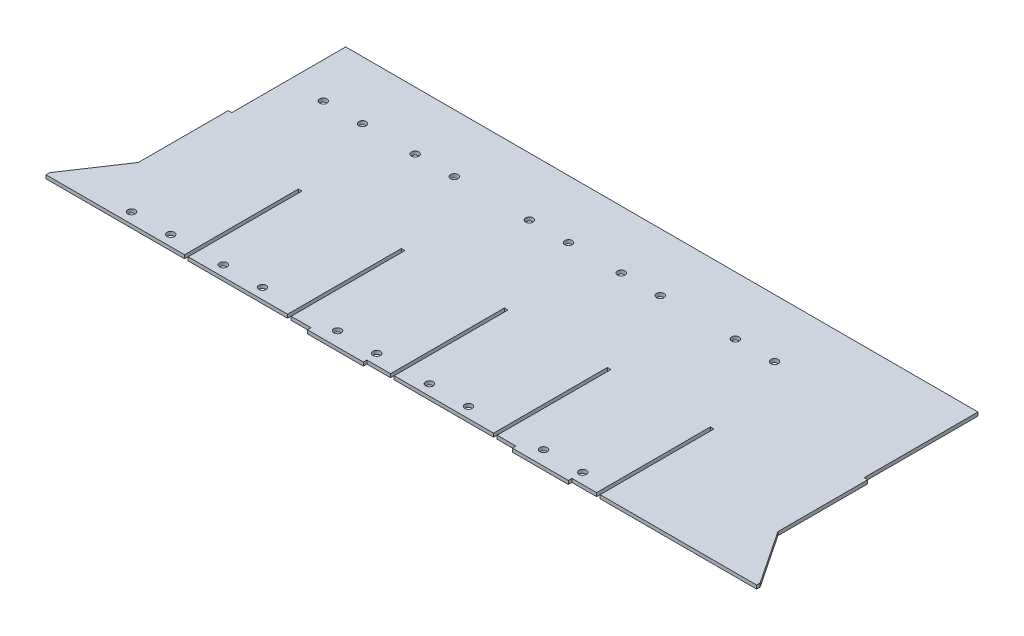
SolidWorks part; units mm, degrees
material "6061-T6 (SS)"
ref_plane "X-Y Datum" through (0, 0, 0) normal (0, 0, 1) x (1, 0, 0)
ref_plane "X-Z Datum" through (0, 0, 0) normal (0, 1, 0) x (1, 0, 0)
ref_plane "Y-Z Datum" through (0, 0, 0) normal (1, 0, 0) x (0, 0, -1)
sketch "Sketch1" plane through (0, 0, 0) normal (0, 0, 1) x (1, 0, 0)
  line L1 (-285.4305, -1.5875) -> (285.4305, -1.5875)
  line L2 (-285.4305, -1.5875) -> (-285.4305, 1.5875)
  line L3 (-285.4305, 1.5875) -> (285.4305, 1.5875)
  line L4 (285.4305, -1.5875) -> (285.4305, 1.5875)
  line L5 (-285.4305, -1.5875) -> (285.4305, 1.5875) construction
  line L6 (-285.4305, 1.5875) -> (285.4305, -1.5875) construction
  point P0 (0, 0)
  dimension "D1" = 570.861
  dimension "D2" = 3.175
extrude "Boss-Extrude1" add sketch "Sketch1" along normal blind 232.6
sketch "Sketch2" plane through (0, 1.5875, 0) normal (0, 1, 0) x (1, 0, 0)
  line L0 (-176.5505, -181.8) -> (-285.4305, -181.8) construction
  line L1 (-285.4305, -232.6) -> (-285.4305, 0) construction
  line L3 (285.4305, -232.6) -> (-285.4305, -232.6) construction
  line L4 (-178.0615, -232.6) -> (-174.8865, -232.6)
  line L6 (-178.0615, -118.3) -> (-174.8865, -118.3)
  line L8 (-178.0615, -232.6) -> (-174.8865, -232.6)
  line L9 (-178.0615, -232.6) -> (-178.0615, -118.3)
  line L10 (-178.0615, -118.3) -> (-174.8865, -118.3)
  line L11 (-174.8865, -232.6) -> (-174.8865, -118.3)
  line L17 (-178.0615, -118.3) -> (-174.8865, -118.3)
  line L38 (-285.4305, 0) -> (-282.2555, 0)
  line L39 (-285.4305, 0) -> (-285.4305, -101.6)
  line L40 (-285.4305, -101.6) -> (-282.2555, -101.6)
  line L41 (-282.2555, 0) -> (-282.2555, -101.6)
  line L42 (285.4305, 0) -> (282.2555, 0)
  line L43 (285.4305, 0) -> (285.4305, -101.6)
  line L44 (285.4305, -101.6) -> (282.2555, -101.6)
  line L45 (282.2555, 0) -> (282.2555, -101.6)
  line M3 (285.4305, 0) -> (-285.4305, 0)
  line M4 (-285.4305, 0) -> (-285.4305, -232.6)
  line M6 (285.4305, -232.6) -> (285.4305, 0)
  dimension "D2" = 50.8
  dimension "D3" = 3.175
  dimension "D6" = 3.175
  dimension "D7" = 101.6
  dimension "D4" = 114.3
  dimension "D8" = 3.175
  dimension "D9" = 101.6
sketch "Sketch6" plane through (0, 0, 232.6) normal (0, 0, 1) x (1, 0, 0)
  line L0 (285.4305, 1.5875) -> (-285.4305, 1.5875) construction
  line L1 (-285.4305, 1.5875) -> (-285.4305, -1.5875) construction
  line L14 (152.263, -1.5875) -> (152.263, 1.5875)
  line L15 (102.263, 1.5875) -> (152.263, 1.5875)
  line L16 (102.263, -1.5875) -> (152.263, 1.5875) construction
  line L17 (102.263, 1.5875) -> (152.263, -1.5875) construction
  line L18 (102.263, -1.5875) -> (152.263, -1.5875)
  line L19 (102.263, -1.5875) -> (102.263, 1.5875)
  line L20 (-30.6951, -1.5875) -> (-30.6951, 1.5875)
  line L21 (-80.6951, 1.5875) -> (-30.6951, 1.5875)
  line L22 (-80.6951, -1.5875) -> (-30.6951, 1.5875) construction
  line L23 (-80.6951, 1.5875) -> (-30.6951, -1.5875) construction
  line L24 (-80.6951, -1.5875) -> (-30.6951, -1.5875)
  line L25 (-80.6951, -1.5875) -> (-80.6951, 1.5875)
  point P4 (-55.6951, 0)
  point P5 (127.263, 0)
  dimension "D1" = 3.175
  dimension "D2" = 50
  dimension "D3" = 3.175
  dimension "D4" = 229.7354
  dimension "D5" = 182.9581
sketch "Sketch7" plane through (0, -1.5875, 0) normal (0, -1, 0) x (-1, 0, 0)
  line L1 (-285.4305, -232.6) -> (-285.4305, 0) construction
  circle A2 centre (-245.6805, -11.2916) radius 3.302
  dimension "D1" = 39.75
  dimension "D2" = 6.604
extrude "Cut-Extrude4" [suppressed] cut sketch "Sketch7" against normal through all contours A2
extrude "Boss-Extrude2" add sketch "Sketch6" along normal blind 3.175
pattern_linear "LPattern1" [suppressed] count 6 spacing 93.98 of bodies 119
extrude "Cut-Extrude5" cut sketch "Sketch2" against normal through all contours L41 L40 M3 M4 | L45 L44 M3 M6 region at (283.843, 1.5875, 50.8) region at (-283.843, 1.5875, 50.8)
sketch "Sketch12" plane through (0, 1.5875, 0) normal (0, 1, 0) x (1, 0, 0)
  line L0 (-285.4305, -232.6) -> (-285.4305, -101.6) construction
  line L1 (-285.4305, -232.6) -> (-285.4305, -181.8)
  line L2 (285.4305, -232.6) -> (285.4305, -101.6) construction
  line L3 (285.4305, -232.6) -> (285.4305, -101.6)
  line L4 (-285.4305, -232.6) -> (-317.1805, -232.6)
  line L6 (-317.1805, -232.6) -> (-317.1805, -229.425)
  line L7 (-317.1805, -229.425) -> (-285.4305, -181.8)
  line M9 (-285.4305, -101.6) -> (-285.4305, -232.6)
  dimension "D1" = 31.75
  dimension "D2" = 50.8
  dimension "D3" = 3.175
extrude "Boss-Extrude3" add sketch "Sketch12" against normal blind 3.175 contours L4 M9 region at (-296.6364, 1.5875, 215.6044)
mirror "Mirror1" about plane through (0, 0, 0) normal (1, 0, 0) of "Boss-Extrude3"
sketch "Sketch13" plane through (0, -1.5875, 0) normal (0, -1, 0) x (1, 0, 0)
  line L0 (-193.4755, 232.6) -> (-193.4755, 131)
  line L1 (-317.1805, 232.6) -> (-80.6951, 232.6) construction
  line L2 (-282.2555, 0) -> (-282.2555, 101.6) construction
  line L3 (-193.4755, 232.6) -> (-190.3005, 232.6)
  line L5 (-193.4755, 232.6) -> (-193.4755, 131)
  line L6 (-193.4755, 131) -> (-190.3005, 131)
  line L7 (-190.3005, 232.6) -> (-190.3005, 131)
  line M23 (-80.6951, 232.6) -> (-317.1805, 232.6)
  dimension "D1" = 88.78
  dimension "D2" = 101.6
  dimension "D3" = 3.175
extrude "Cut-Extrude6" cut sketch "Sketch13" against normal through all contours L7 L0 L6 M23 region at (-191.888, -1.5875, 181.8)
pattern_linear "LPattern2" count 5 spacing 91.955 along (1, 0, 0) of "Cut-Extrude6"
sketch "Sketch14" plane through (0, 1.5875, 0) normal (0, 1, 0) x (1, 0, 0)
  circle A0 centre (-215.403, -51.825) radius 3 construction
  circle A1 centre (-250.328, -51.825) radius 3 construction
  circle A2 centre (-215.403, -223.075) radius 3 construction
  circle A3 centre (-250.328, -223.075) radius 3 construction
  circle A4 centre (-215.403, -51.825) radius 3 construction
  circle A5 centre (-250.328, -51.825) radius 3 construction
  circle A6 centre (-215.403, -223.075) radius 3 construction
  circle A7 centre (-250.328, -223.075) radius 3 construction
  circle A8 centre (-133.4455, -51.825) radius 3.3 construction
  circle A9 centre (-168.3705, -51.825) radius 3.3 construction
  circle A10 centre (-133.4455, -223.075) radius 3.3 construction
  circle A11 centre (-168.3705, -223.075) radius 3.3 construction
  circle A12 centre (-133.4455, -51.825) radius 3.3 construction
  circle A13 centre (-168.3705, -51.825) radius 3.3 construction
  circle A14 centre (-133.4455, -223.075) radius 3.3 construction
  circle A15 centre (-168.3705, -223.075) radius 3.3 construction
hole_wizard "M6 Clearance Hole1" positions "Sketch15" profile "Sketch16" hole size "M6" standard "ANSI Metric" end condition through all
sketch "Sketch15" plane through (0, 1.5875, 0) normal (0, 1, 0) x (1, 0, 0)
  point P0 (-250.328, -223.075)
  point P3 (-215.403, -223.075)
  point P6 (-215.403, -51.825)
  point P9 (-250.328, -51.825)
sketch "Sketch16" plane through (-250.328, 1.5875, 223.075) normal (1, 0, 0) x (0, 0, 1)
  line L0 (0, 0) -> (0, 3.175)
  line L1 (0, 3.175) -> (3.3, 3.175)
  line L2 (3.3, 3.175) -> (3.3, 0)
  line L5 (3.3, 0) -> (0, 0)
  line L11 (0, -6.35) -> (0, 107.95) construction
  dimension "Thru Hole Dia." = 6.6
  dimension "Thru Hole Depth" = 3.175
hole_wizard "M6 Clearance Hole2" positions "Sketch17" profile "Sketch18" hole size "M6" standard "ANSI Metric" end condition through all
sketch "Sketch17" plane through (0, 1.5875, 0) normal (0, 1, 0) x (1, 0, 0)
  point P0 (-168.3705, -223.075)
  point P3 (-133.4455, -223.075)
  point P6 (-168.3705, -51.825)
  point P9 (-133.4455, -51.825)
sketch "Sketch18" plane through (-168.3705, 1.5875, 223.075) normal (1, 0, 0) x (0, 0, 1)
  line L0 (0, 0) -> (0, 3.175)
  line L1 (0, 3.175) -> (3.3, 3.175)
  line L2 (3.3, 3.175) -> (3.3, 0)
  line L5 (3.3, 0) -> (0, 0)
  line L11 (0, -6.35) -> (0, 107.95) construction
  dimension "Thru Hole Dia." = 6.6
  dimension "Thru Hole Depth" = 3.175
pattern_linear "LPattern3" count 3 spacing 183.92 along (1, 0, 0) of "M6 Clearance Hole1"
pattern_linear "LPattern4" count 2 spacing 183.92 along (1, 0, 0) of "M6 Clearance Hole2"
